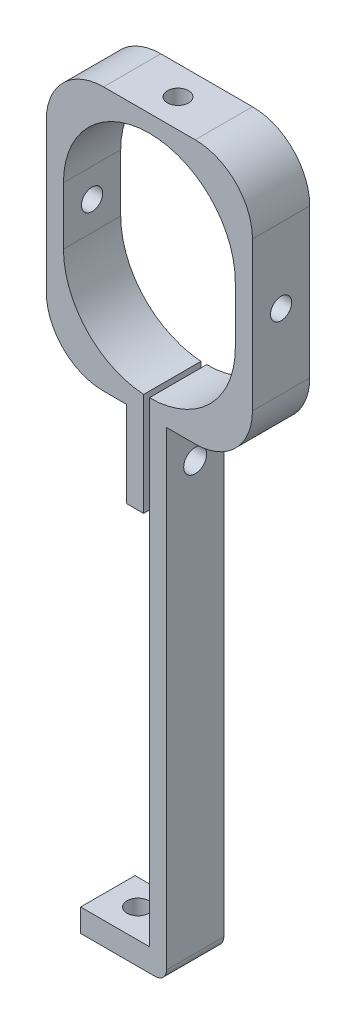
SolidWorks part; units mm, degrees
ref_plane "Front Plane" through (0, 0, 0) normal (0, 0, 1) x (1, 0, 0)
ref_plane "Top Plane" through (0, 0, 0) normal (0, 1, 0) x (1, 0, 0)
ref_plane "Right Plane" through (0, 0, 0) normal (1, 0, 0) x (0, 0, -1)
sketch "Sketch2" plane through (0, 0, 0) normal (0, 0, 1) x (1, 0, 0)
  line L0 (15, 0) -> (30, 0)
  line L1 (0, 0) -> (14, 0)
  line L2 (0, 0) -> (0, 40)
  line L3 (0, 40) -> (30, 40)
  line L4 (30, 0) -> (30, 40)
  line L13 (14, 0) -> (14, -80)
  line L14 (14, -80) -> (15, -80)
  line L15 (15, -80) -> (15, 0)
  line L16 (18, -3) -> (33, -3)
  line L17 (33, -3) -> (33, 43)
  line L18 (-3, 43) -> (33, 43)
  line L19 (-3, -3) -> (-3, 43)
  line L20 (-3, -3) -> (11, -3)
  line L21 (11, -3) -> (11, -83)
  line L22 (11, -83) -> (18, -83)
  line L23 (18, -83) -> (18, -3)
  dimension "D1" = 40
  dimension "D2" = 30
  dimension "D3" = 1
  dimension "D4" = 80
  dimension "D5" = 14
  dimension "D6" = 3
extrude "Boss-Extrude2" add sketch "Sketch2" along normal blind 10
sketch "Sketch5" plane through (0, 0, 10) normal (0, 0, 1) x (1, 0, 0)
  line L0 (4, -3) -> (4, -18) construction
  line L5 (15, -80) -> (15, -85.4078) construction
  line L7 (-3, -3) -> (11, -3) construction
  line L9 (4, -18) -> (15, -18)
  line L10 (4, -18) -> (4, -85.4078)
  line L11 (4, -85.4078) -> (15, -85.4078)
  line L12 (15, -18) -> (15, -85.4078)
  dimension "D1" = 15
extrude "Cut-Extrude2" cut sketch "Sketch5" against normal through all both and the other way through all
sketch "Sketch9" plane through (0, 0, 0) normal (0, 0, -1) x (-1, 0, 0)
  line L0 (-15, 43) -> (-15, 93.655) construction
  line L1 (-33, 43) -> (3, 43) construction
  line L2 (-35, 43) -> (5, 43)
  line L3 (5, 43) -> (25, 43) construction
  line L4 (25, 43) -> (25, 53) construction
  line L5 (5, 43) -> (20.6456, 50.8228)
  line L6 (25, 53) -> (45, 53) construction
  line L7 (45, 53) -> (45, 73) construction
  line L9 (45, 85.4264) -> (45, 113)
  line L10 (3, 43) -> (3, -3) construction
  line L11 (-75, 53) -> (-75, 73) construction
  line L12 (-55, 53) -> (-75, 53) construction
  line L13 (-70, 85.4264) -> (-70, 113)
  line L14 (-55, 43) -> (-55, 53) construction
  line L15 (-35, 43) -> (-55, 43) construction
  line L16 (-75, 85.4264) -> (-75, 113)
  line L17 (-58.4424, 56.4424) -> (-66.2132, 64.2132)
  line L18 (-35, 43) -> (-50.6456, 50.8228)
  line L19 (-54.9069, 59.978) -> (-62.6777, 67.7487)
  line L20 (-33.8197, 48) -> (-48.4096, 55.295)
  line L21 (-33.8197, 48) -> (3.8197, 48)
  line L22 (3.8197, 48) -> (18.4096, 55.295)
  line L24 (40, 85.4264) -> (40, 113)
  line L25 (-75, 113) -> (-70, 113)
  line L26 (40, 113) -> (45, 113)
  line L27 (40, 85.4264) -> (18.4096, 55.295)
  line L28 (20.6456, 50.8228) -> (36.2132, 64.2132)
  line L29 (45, 85.4264) -> (36.2132, 64.2132)
  line L31 (24.9069, 59.978) -> (32.6777, 67.7487) construction
  line L32 (28.4424, 56.4424) -> (36.2132, 64.2132) construction
  arc A2 (-58.4424, 56.4424) -> (-50.6456, 50.8228) centre (-37.2292, 77.6556) ccw
  arc A3 (-66.2132, 64.2132) -> (-75, 85.4264) centre (-45, 85.4264) cw
  arc A4 (-62.6777, 67.7487) -> (-70, 85.4264) centre (-45, 85.4264) cw
  arc A5 (-54.9069, 59.978) -> (-48.4096, 55.295) centre (-37.2292, 77.6556) ccw
  arc A8 (40, 85.4264) -> (32.6777, 67.7487) centre (15, 85.4264) cw construction
  arc A9 (24.9069, 59.978) -> (18.4096, 55.295) centre (7.2292, 77.6556) cw construction
  arc A10 (28.4424, 56.4424) -> (20.6456, 50.8228) centre (7.2292, 77.6556) cw construction
  arc A11 (45, 85.4264) -> (36.2132, 64.2132) centre (15, 85.4264) cw construction
  dimension "D7" = 21.2132
  dimension "D1" = 20
  dimension "D2" = 20
  dimension "D3" = 10
  dimension "D4" = 20
  dimension "D5" = 20
  dimension "D6" = 40
  dimension "D8" = 5
  dimension "D9" = 20.5342
  dimension "D10" = 15.6456
sketch "Sketch16" plane through (11, 0, 0) normal (-1, 0, 0) x (0, 0, 1)
  line L0 (0, -18) -> (10, -3) construction
  line L1 (0, -3) -> (10, -18) construction
  circle A0 centre (5, -10.5) radius 1.85
  dimension "D1" = 3.7
extrude "Cut-Extrude3" cut sketch "Sketch16" against normal through all both and the other way through all
fillet "Fillet16" radius 15 4 edges at (0, 40, 5) (30, 40, 5) (0, 0, 5) (30, 0, 5)
sketch "Sketch41" plane through (18, 0, 0) normal (1, 0, 0) x (0, 0, -1)
  line L0 (0, -83) -> (-20, -83) construction
  circle A0 centre (-20, -83) radius 20
  dimension "D1" = 20
sketch "Sketch44" plane through (0, 0, 0) normal (0, 0, -1) x (-1, 0, 0)
sketch "Sketch45" plane through (-3, 0, 0) normal (-1, 0, 0) x (0, 0, 1)
  line L0 (0, 43) -> (10, -3) construction
  line L1 (10, -3) -> (10, 43) construction
  line L2 (10, 43) -> (0, -3) construction
  circle A0 centre (5, 20) radius 1.85
  dimension "D1" = 3.7
extrude "Cut-Extrude20" cut sketch "Sketch45" against normal through all both and the other way through all
sketch "Sketch46" plane through (0, 43, 0) normal (0, 1, 0) x (1, 0, 0)
  line L0 (-3, -10) -> (33, 0) construction
  line L1 (33, 0) -> (-3, 0) construction
  line L2 (-3, 0) -> (33, -10) construction
  line L3 (33, -10) -> (33, 0) construction
  circle A0 centre (15, -5) radius 1.85
  dimension "D1" = 3.7
sketch "Sketch48" plane through (-3, 0, 0) normal (-1, 0, 0) x (0, 0, 1)
  line L0 (5, 43) -> (5, 38.4589) construction
  line L1 (10, 43) -> (0, 43) construction
  line L3 (7, 45) -> (3, 45)
  line L4 (7, 45) -> (7, 41)
  line L5 (7, 41) -> (3, 41)
  line L6 (3, 45) -> (3, 41)
  line L7 (7, 45) -> (3, 41) construction
  line L8 (7, 41) -> (3, 45) construction
  dimension "D1" = 4
  dimension "D2" = 4
sketch "Sketch52" plane through (0, -83, 0) normal (0, -1, 0) x (1, 0, 0)
  line L1 (18, 10) -> (3, 10)
  line L2 (18, 10) -> (18, 0)
  line L3 (18, 0) -> (3, 0)
  line L4 (3, 10) -> (3, 0)
  dimension "D1" = 15
  dimension "D2" = 10
extrude "Boss-Extrude25" add sketch "Sketch52" along normal blind 4
fillet "Fillet17" radius 10 2 edges at (-3, -3, 5) (33, -3, 5)
fillet "Fillet18" radius 2 1 edges at (18, -87, 5)
sketch "Sketch53" plane through (0, -87, 0) normal (0, -1, 0) x (1, 0, 0)
  line L0 (16, 5) -> (0, 5) construction
  line L1 (16, 0) -> (16, 10) construction
  line L2 (3, 10) -> (3, 0) construction
  circle A0 centre (8, 5) radius 1.9
  dimension "D1" = 3.8
  dimension "D2" = 5
extrude "Cut-Extrude25" cut sketch "Sketch53" against normal blind 10
sketch "Sketch54" plane through (3, 0, 0) normal (-1, 0, 0) x (0, 0, 1)
  line L0 (10, -87) -> (0, -87) construction
  line L2 (0, -83) -> (0.5, -83)
  line L3 (0, -83) -> (0, -87)
  line L4 (0, -87) -> (0.5, -87)
  line L5 (0.5, -83) -> (0.5, -87)
  line L6 (10, -83) -> (9.5, -83)
  line L7 (10, -83) -> (10, -87)
  line L8 (10, -87) -> (9.5, -87)
  line L9 (9.5, -83) -> (9.5, -87)
  dimension "D1" = 0.5
  dimension "D2" = 0.5
sketch "Sketch55" plane through (3, 0, 0) normal (-1, 0, 0) x (0, 0, 1)
  line L0 (10, -87) -> (0, -87) construction
  line L1 (0, -83) -> (0.5, -83)
  line L2 (0, -83) -> (0, -87)
  line L3 (0, -87) -> (0.5, -87)
  line L4 (0.5, -83) -> (0.5, -87)
  dimension "D1" = 0.5
extrude "Cut-Extrude28" cut sketch "Sketch55" against normal blind 10
sketch "Sketch56" plane through (-3, 0, 0) normal (-1, 0, 0) x (0, 0, 1)
  line L1 (10, 43) -> (0, 43)
  line L2 (10, 43) -> (10, 47)
  line L3 (10, 47) -> (0, 47)
  line L4 (0, 43) -> (0, 47)
  dimension "D1" = 4
sketch "Sketch60" plane through (18, 0, 0) normal (1, 0, 0) x (0, 0, -1)
  line L0 (-5, -8.65) -> (-5, -12.35) construction
  line L1 (-5, -12.35) -> (-3.15, -10.5) construction
  line L2 (-3.15, -10.5) -> (-6.85, -10.5) construction
  circle A0 centre (-5, -10.5) radius 1.85 construction
  circle A1 centre (-5, -10.5) radius 2
  dimension "D1" = 4
extrude "Cut-Extrude32" cut sketch "Sketch60" against normal through all both and the other way through all
fillet "Fillet19" radius 10 2 edges at (33, 43, 5) (-3, 43, 5)
sketch "Sketch61" plane through (0, 43, 0) normal (0, 1, 0) x (1, 0, 0)
  line L0 (15, 0) -> (15, -10) construction
  line L1 (23, 0) -> (7, 0) construction
  line L2 (23, -10) -> (7, -10) construction
  circle A0 centre (15, -5) radius 1.85
  dimension "D1" = 3.7
extrude "Cut-Extrude33" cut sketch "Sketch61" against normal blind 10
